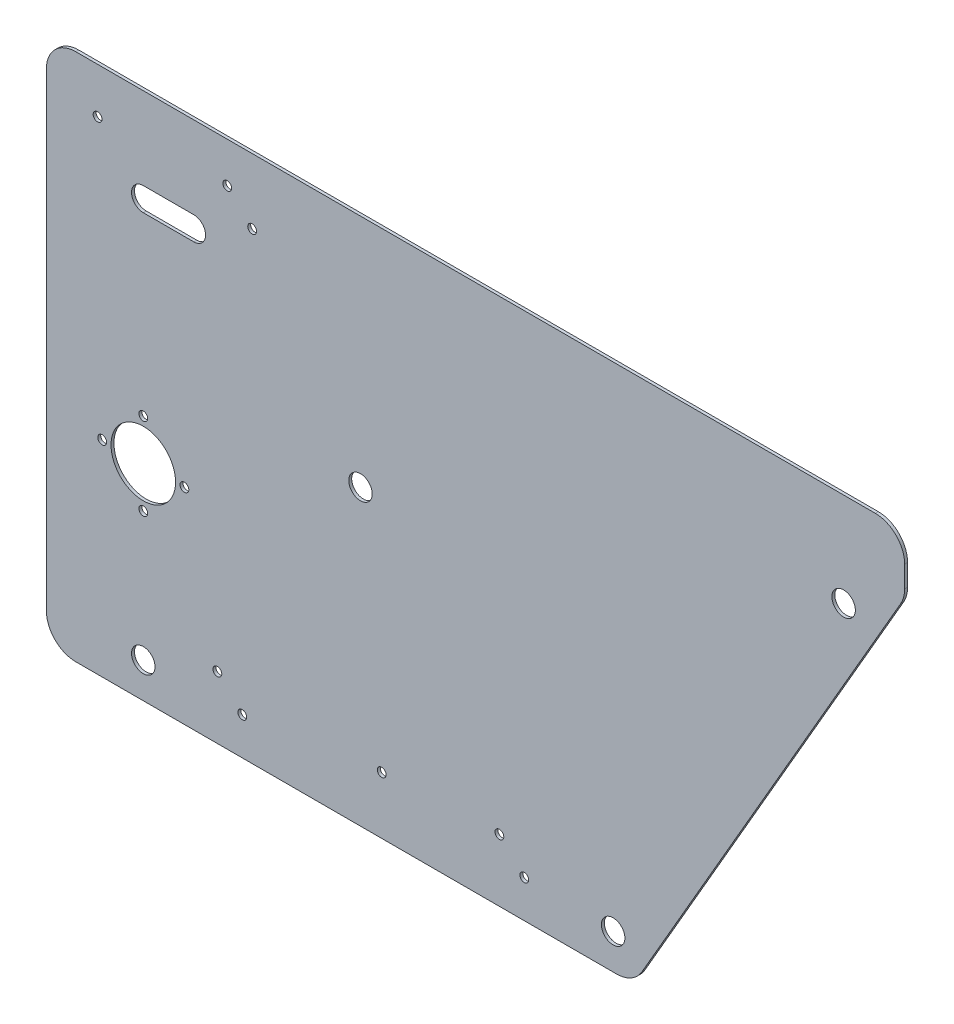
SolidWorks part; units mm, degrees
ref_plane "Front Plane" through (0, 0, 0) normal (0, 0, 1) x (1, 0, 0)
ref_plane "Top Plane" through (0, 0, 0) normal (0, 1, 0) x (1, 0, 0)
ref_plane "Right Plane" through (0, 0, 0) normal (1, 0, 0) x (0, 0, -1)
sketch "Sketch1" plane through (0, 0, 0) normal (0, 0, 1) x (1, 0, 0)
  line L0 (100, 80) -> (192.376, 80)
  line L1 (-100, -80) -> (100, -80)
  line L2 (-100, -80) -> (-100, 80)
  line L3 (-100, 80) -> (100, 80)
  line L4 (100, -80) -> (100, 80)
  line L5 (-100, -80) -> (100, 80) construction
  line L6 (-100, 80) -> (100, -80) construction
  line L7 (192.376, 80) -> (100, -80)
  line L8 (100, 80) -> (100, -80)
  line L10 (-100, 80) -> (192.376, 80)
  line L11 (-100, 80) -> (-100, 100)
  line L12 (-100, 100) -> (192.376, 100)
  line L13 (192.376, 80) -> (192.376, 100)
  point P0 (0, 0)
  dimension "D1" = 160
  dimension "D2" = 200
  dimension "D3" = 30
  dimension "D4" = 20
extrude "Boss-Extrude1" add sketch "Sketch1" along normal blind 1 contours L1 L4 L3 L2 | L7 L0 L4 | L11 L10 L13 L12 region at (0, 0, 0) region at (130.792, 26.6667, 0)
fillet "Fillet1" radius 10 5 edges at (100, -80, 0.5) (-100, -80, 0.5) (192.376, 100, 0.5) (-100, 100, 0.5) (192.376, 80, 0.5)
sketch "Sketch2" plane through (0, 0, 1) normal (0, 0, 1) x (1, 0, 0)
  line L0 (-90, -80) -> (94.2265, -80) construction
  line L1 (191.0363, 77.6795) -> (102.8868, -75) construction
  line L3 (-90, 100) -> (182.376, 100) construction
  line L4 (-67, 68) -> (-49.7837, 68) construction
  line L7 (-100, -70) -> (-100, 90) construction
  line L9 (-67, 72) -> (-49.7837, 72)
  line L10 (-67, 64) -> (-49.7837, 64)
  circle A0 centre (93.0718, -68) radius 4
  circle A1 centre (171.5914, 68) radius 4
  circle A2 centre (-67, -10) radius 11
  circle A3 centre (-67, -68) radius 4
  circle A4 centre (-53, -10) radius 1.5
  circle A5 centre (-67, 4) radius 1.5
  circle A6 centre (-81, -10) radius 1.5
  circle A7 centre (-67, -24) radius 1.5
  circle A10 centre (6.9988, 20) radius 4
  arc A11 (-67, 72) -> (-67, 64) centre (-67, 68) ccw
  arc A12 (-49.7837, 64) -> (-49.7837, 72) centre (-49.7837, 68) ccw
  circle A32 centre (62.7961, -67.2426) radius 1.5
  circle A33 centre (54.3108, -58.7574) radius 1.5
  circle A34 centre (-33.2742, -67.2426) radius 1.5
  circle A35 centre (-41.7595, -58.7574) radius 1.5
  circle A36 centre (14.2259, -60.5) radius 1.5
  circle A37 centre (-29.9152, 77.7574) radius 1.5
  circle A38 centre (-38.4005, 86.2426) radius 1.5
  circle A39 centre (-82.5763, 84.5) radius 1.5
  point P12 (-58.3919, 68)
  dimension "D3" = 8
  dimension "D4" = 8
  dimension "D9" = 22
  dimension "D10" = 8
  dimension "D12" = 3
  dimension "D13" = 3
  dimension "D14" = 3
  dimension "D15" = 3
  dimension "D16" = 14
  dimension "D20" = 4
  dimension "D22" = 8
  dimension "D23" = 3
  dimension "D1" = 12
  dimension "D2" = 12
  dimension "D5" = 32
  dimension "D6" = 12
  dimension "D7" = 33
  dimension "D8" = 70
  dimension "D11" = 12
  dimension "D17" = 14
  dimension "D18" = 14
  dimension "D19" = 14
  dimension "D21" = 80
extrude "Cut-Extrude1" cut sketch "Sketch2" against normal blind 3
